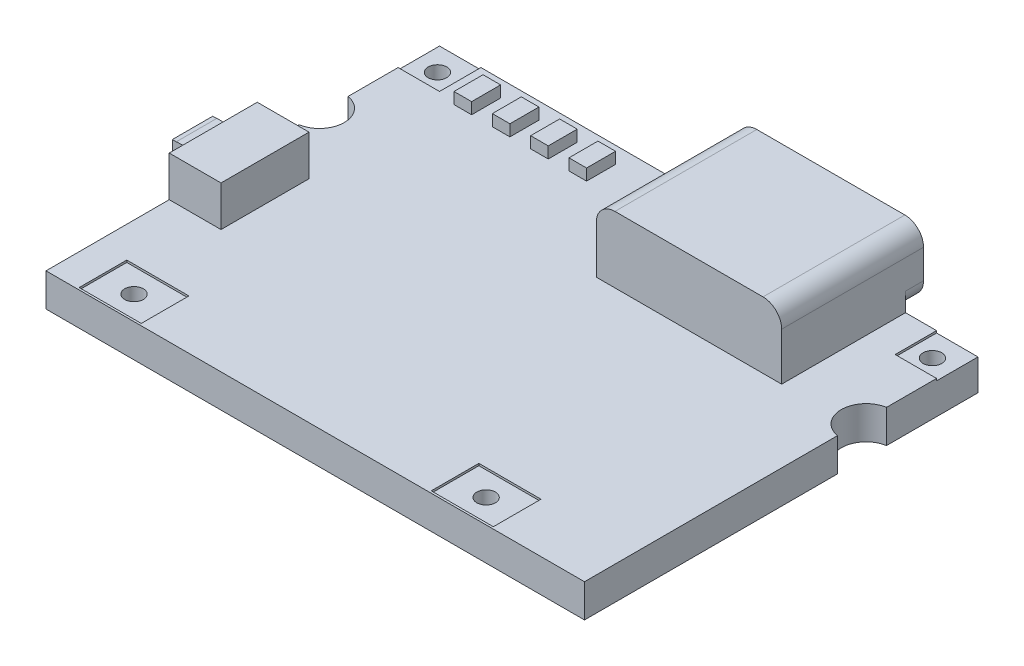
SolidWorks part; units mm, degrees
ref_plane "Front Plane" through (0, 0, 0) normal (0, 0, 1) x (1, 0, 0)
ref_plane "Top Plane" through (0, 0, 0) normal (0, 1, 0) x (1, 0, 0)
ref_plane "Right Plane" through (0, 0, 0) normal (1, 0, 0) x (0, 0, -1)
ref_axis "X-Axis" through (-88.99, 0, 0) along (1, 0, 0)
ref_axis "Y-Axis" through (0, 55, 0) along (0, -1, 0)
ref_axis "Z-Axis" through (0, 0, -88.99) along (0, 0, 1)
sketch "Sketch1" plane through (0, 0, 0) normal (0, 1, 0) x (1, 0, 0)
  line L1 (-13, -9.5) -> (13, -9.5)
  line L2 (-13, -9.5) -> (-13, 9.5)
  line L3 (-13, 9.5) -> (13, 9.5)
  line L4 (13, -9.5) -> (13, 9.5)
  line L5 (-13, -9.5) -> (13, 9.5) construction
  line L6 (-13, 9.5) -> (13, -9.5) construction
  point P0 (0, 0)
  dimension "D1" = 26
  dimension "D2" = 19
extrude "Boss-Extrude1" add sketch "Sketch1" along normal blind 1.6
sketch "Sketch2" plane through (0, 1.6, 0) normal (0, 1, 0) x (1, 0, 0)
  line L1 (0.55, 10.37) -> (9.5, 10.37)
  line L2 (0.55, 10.37) -> (0.55, 3.52)
  line L3 (0.55, 3.52) -> (9.5, 3.52)
  line L4 (9.5, 10.37) -> (9.5, 3.52)
  line L5 (13, 9.5) -> (-13, 9.5) construction
  line L6 (13, -9.5) -> (13, 9.5) construction
  dimension "D1" = 8.95
  dimension "D2" = 6.85
  dimension "D3" = 0.87
  dimension "D4" = 3.5
extrude "Boss-Extrude2" add sketch "Sketch2" along normal blind 3.2
sketch "Sketch3" plane through (0, 1.6, 0) normal (0, 1, 0) x (1, 0, 0)
  line L0 (-13, -8.25) -> (-10, -8.25) construction
  line L1 (-13, -9.5) -> (13, -9.5) construction
  line L4 (-13, 9.5) -> (-13, -9.5) construction
  line L5 (-10, -8.25) -> (7, -8.25) construction
  line L6 (7, -8.25) -> (13, -8.25) construction
  line L7 (13, -9.5) -> (13, 9.5) construction
  circle A0 centre (-10, -8.25) radius 0.45
  circle A1 centre (7, -8.25) radius 0.45
  point P10 (7, -8.7)
  dimension "D2" = 0.9
  dimension "D1" = 17
  dimension "D3" = 0.8
  dimension "D4" = 6
extrude "Cut-Extrude1" cut sketch "Sketch3" against normal through all
sketch "Sketch4" plane through (0, 1.6, 0) normal (0, 1, 0) x (1, 0, 0)
  line L0 (-13.2, 3.9) -> (13.2, 3.9) construction
  line L4 (13, 9.5) -> (9.5, 9.5) construction
  line L5 (-13, 9.5) -> (-13, -9.5) construction
  line L6 (13, -9.5) -> (13, 9.5) construction
  circle A0 centre (-13.2, 3.9) radius 1.2
  circle A1 centre (13.2, 3.9) radius 1.2
  point P2 (-12, 3.9)
  point P3 (12, 3.9)
  point P8 (13.2, 5.1)
  dimension "D1" = 2.4
  dimension "D2" = 4.4
  dimension "D3" = 1
  dimension "D4" = 1
extrude "Cut-Extrude2" cut sketch "Sketch4" against normal through all
sketch "Sketch5" plane through (0, 1.6, 0) normal (0, 1, 0) x (1, 0, 0)
  line L0 (-12.4, 8.35) -> (12.4, 8.35) construction
  line L1 (-13, 9.5) -> (-13, 5.0832) construction
  line L4 (12.4, 8.35) -> (13, 8.35) construction
  line L5 (13, 5.0832) -> (13, 9.5) construction
  line L6 (-12.4, 8.35) -> (-13, 8.35) construction
  line L7 (13, 9.5) -> (9.5, 9.5) construction
  circle A0 centre (-11.95, 8.35) radius 0.45
  circle A1 centre (11.95, 8.35) radius 0.45
  point P10 (11.95, 8.8)
  point P12 (-11.5, 8.35)
  point P13 (11.5, 8.35)
  dimension "D2" = 0.9
  dimension "D1" = 0.7
  dimension "D3" = 23
extrude "Cut-Extrude3" cut sketch "Sketch5" against normal through all
sketch "Sketch6" plane through (0, 1.6, 0) normal (0, 1, 0) x (1, 0, 0)
  line L1 (-13, 9.5) -> (-11, 9.5)
  line L2 (-13, 9.5) -> (-13, 7.5)
  line L3 (-13, 7.5) -> (-11, 7.5)
  line L4 (-11, 9.5) -> (-11, 7.5)
  line L5 (13, 9.5) -> (11, 9.5)
  line L6 (13, 9.5) -> (13, 7.5)
  line L7 (13, 7.5) -> (11, 7.5)
  line L8 (11, 9.5) -> (11, 7.5)
  line L9 (-11.5, -9.4) -> (-8.5, -9.4)
  line L10 (-11.5, -9.4) -> (-11.5, -7.1)
  line L11 (-11.5, -7.1) -> (-8.5, -7.1)
  line L12 (-8.5, -9.4) -> (-8.5, -7.1)
  line L13 (-11.5, -9.4) -> (-8.5, -7.1) construction
  line L14 (-11.5, -7.1) -> (-8.5, -9.4) construction
  line L15 (5.5, -9.4) -> (8.5, -9.4)
  line L16 (5.5, -9.4) -> (5.5, -7.1)
  line L17 (5.5, -7.1) -> (8.5, -7.1)
  line L18 (8.5, -9.4) -> (8.5, -7.1)
  line L19 (5.5, -9.4) -> (8.5, -7.1) construction
  line L20 (5.5, -7.1) -> (8.5, -9.4) construction
  point P10 (-10, -8.25)
  point P16 (7, -8.25)
  dimension "D1" = 2
  dimension "D2" = 2
  dimension "D3" = 2
  dimension "D4" = 2
  dimension "D5" = 3
  dimension "D6" = 3
  dimension "D7" = 2.3
  dimension "D8" = 2.3
extrude "Cut-Extrude4" cut sketch "Sketch6" against normal blind 0.1
fillet "Fillet1" radius 0.9 4 edges at (0.55, 1.6, -9.935) (0.55, 4.8, -6.945) (9.5, 4.8, -6.945) (9.5, 1.6, -9.935)
sketch "Sketch8" plane through (0, 1.6, 0) normal (0, 1, 0) x (1, 0, 0)
  line L0 (-13, 2.7168) -> (-13, -9.5) construction
  line L1 (-13, 0.7) -> (-10.5, 0.7)
  line L2 (-13, 0.7) -> (-13, -3.55)
  line L3 (-13, -3.55) -> (-10.5, -3.55)
  line L4 (-10.5, 0.7) -> (-10.5, -3.55)
  line L5 (0.55, 9.5) -> (-11, 9.5) construction
  dimension "D1" = 4.25
  dimension "D2" = 2.5
  dimension "D3" = 8.8
extrude "Boss-Extrude3" add sketch "Sketch8" along normal blind 1.95
sketch "Sketch9" plane through (-13, 0, 0) normal (-1, 0, 0) x (0, 0, 1)
  line L0 (-0.7, 2.575) -> (3.55, 2.575) construction
  line L1 (-0.7, 3.55) -> (-0.7, 1.6) construction
  line L2 (3.55, 3.55) -> (3.55, 1.6) construction
  line L4 (0.45, 2.1) -> (2.4, 2.1)
  line L5 (0.45, 2.1) -> (0.45, 3.05)
  line L6 (0.45, 3.05) -> (2.4, 3.05)
  line L7 (2.4, 2.1) -> (2.4, 3.05)
  line L8 (0.45, 2.1) -> (2.4, 3.05) construction
  line L9 (0.45, 3.05) -> (2.4, 2.1) construction
  point P6 (1.425, 2.575)
  dimension "D1" = 1.95
  dimension "D2" = 0.95
extrude "Boss-Extrude4" add sketch "Sketch9" along normal blind 1
sketch "Sketch10" plane through (0, 1.6, 0) normal (0, 1, 0) x (1, 0, 0)
  line L0 (0.55, 9.5) -> (-11, 9.5) construction
  line L1 (-10.1, 8.7) -> (-9.25, 8.7)
  line L2 (-10.1, 8.7) -> (-10.1, 7.3)
  line L3 (-10.1, 7.3) -> (-9.25, 7.3)
  line L4 (-9.25, 8.7) -> (-9.25, 7.3)
  line L5 (-13, 7.5) -> (-13, 5.0832) construction
  dimension "D1" = 0.85
  dimension "D2" = 1.4
  dimension "D3" = 0.8
  dimension "D4" = 2.9
extrude "Boss-Extrude5" add sketch "Sketch10" along normal blind 0.55
pattern_linear "LPattern1" count 4 spacing 1.85 along (1, 0, 0) of "Boss-Extrude5"
sketch "Sketch11" plane through (0, 3.05, 0) normal (0, 1, 0) x (1, 0, 0)
  line L0 (-14, -2.4) -> (-13, -2.4) construction
  line L1 (-14, -0.45) -> (-13.8, -0.45)
  line L2 (-14, -0.45) -> (-14, -2.4)
  line L3 (-14, -2.4) -> (-13.8, -2.4)
  line L4 (-13.8, -0.45) -> (-13.8, -2.4)
  dimension "D1" = 0.2
extrude "Cut-Extrude5" cut sketch "Sketch11" against normal blind 0.01
equation "\"D3@Sketch4\"=\"D4@Sketch4\""
equation "\"D3@LPattern1\"=\"D1@Sketch10\"+1"
